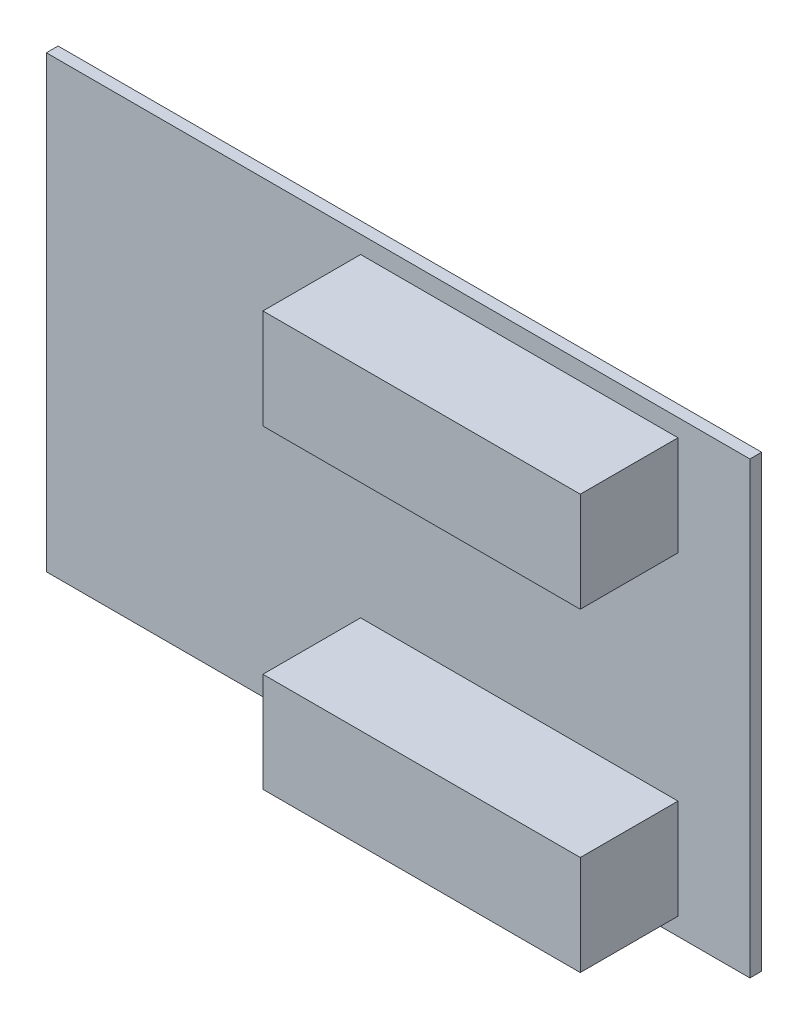
SolidWorks part; units mm, degrees
ref_plane "前视基准面" through (0, 0, 0) normal (0, 0, 1) x (1, 0, 0)
ref_plane "上视基准面" through (0, 0, 0) normal (0, 1, 0) x (1, 0, 0)
ref_plane "右视基准面" through (0, 0, 0) normal (1, 0, 0) x (0, 0, -1)
sketch "草图1" plane through (0, 0, 0) normal (0, 0, 1) x (1, 0, 0)
  line L1 (-90, 57.5) -> (90, 57.5)
  line L2 (-90, 57.5) -> (-90, -57.5)
  line L3 (-90, -57.5) -> (90, -57.5)
  line L4 (90, 57.5) -> (90, -57.5)
  line L5 (-90, 57.5) -> (90, -57.5) construction
  line L6 (-90, -57.5) -> (90, 57.5) construction
  point P0 (0, 0)
  dimension "D1" = 115
  dimension "D2" = 180
extrude "凸台-拉伸1" add sketch "草图1" along normal blind 3
sketch "草图7" plane through (0, 0, 0) normal (0, 0, -1) x (-1, 0, 0)
  line L0 (-90, 57.5) -> (90, 57.5) construction
  line L1 (-69.1, 50.5) -> (7.1, 50.5)
  line L2 (-69.1, 50.5) -> (-69.1, 30)
  line L3 (-69.1, 30) -> (7.1, 30)
  line L4 (7.1, 50.5) -> (7.1, 30)
  line L6 (-90, -57.5) -> (-90, 57.5) construction
  dimension "D1" = 20.5
  dimension "D2" = 76.2
  dimension "D3" = 7
  dimension "D4" = 20.9
extrude "电池位切除-拉伸3" cut sketch "草图7" against normal up to next
sketch "草图8" plane through (0, 0, 3) normal (0, 0, 1) x (1, 0, 0)
  line L12 (69.1, 50.5) -> (69.1, 30) construction
  line L13 (-9.6, 53) -> (71.6, 53)
  line L14 (-9.6, 53) -> (-9.6, 27.5)
  line L15 (-9.6, 27.5) -> (71.6, 27.5)
  line L16 (71.6, 53) -> (71.6, 27.5)
  line L17 (-7.1, 30) -> (-7.1, 50.5) construction
  line L18 (-7.1, 50.5) -> (69.1, 50.5) construction
  line L19 (69.1, 30) -> (-7.1, 30) construction
  line L20 (-7.1, 50.5) -> (69.1, 50.5)
  line L21 (69.1, 30) -> (-7.1, 30)
  line L22 (69.1, 50.5) -> (69.1, 30)
  line L23 (-7.1, 30) -> (-7.1, 50.5) construction
  line L24 (-7.1, 30) -> (-7.1, 50.5)
  dimension "D1" = 2.5
  dimension "D2" = 2.5
  dimension "D3" = 2.5
  dimension "D4" = 2.5
extrude "凸台-拉伸2" add sketch "草图8" along normal blind 25
sketch "草图9" plane through (0, 0, 28) normal (0, 0, 1) x (1, 0, 0)
  line L0 (71.6, 53) -> (-9.6, 53) construction
  line L5 (71.6, 53) -> (-9.6, 53)
  line L6 (-9.6, 27.5) -> (71.6, 27.5) construction
  line L7 (-9.6, 27.5) -> (71.6, 27.5)
  line L8 (71.6, 27.5) -> (71.6, 53) construction
  line L9 (71.6, 27.5) -> (71.6, 53)
  line L10 (-9.6, 53) -> (-9.6, 27.5) construction
  line L11 (-9.6, 53) -> (-9.6, 27.5)
extrude "凸台-拉伸3" add sketch "草图9" against normal blind 2.5
sketch "草图4" plane through (0, 0, 0) normal (0, 0, -1) x (-1, 0, 0)
  line L0 (7.1, 30) -> (7.1, 50.5) construction
  line L5 (7.1, 40.25) -> (84.6307, 40.25) construction
  line L10 (83.2374, -53.4277) -> (79.3374, -53.4277) construction
  line L11 (83.2374, -49.6277) -> (83.2374, -53.4277) construction
  line L12 (79.3374, -49.6277) -> (83.2374, -49.6277) construction
  line L29 (7.1, 36.25) -> (11.1, 36.25)
  line L30 (11.1, 36.25) -> (11.1, 44.25)
  line L31 (11.1, 44.25) -> (7.1, 44.25)
  line L32 (7.1, 44.25) -> (7.1, 36.25)
  dimension "D1" = 8
  dimension "D2" = 4
extrude "切除-拉伸2" cut sketch "草图4" along normal blind 1.6 from surface starting at face at (0, 0, 3)
mirror "镜向1" about plane through (0, 0, 0) normal (0, 1, 0) of "切除-拉伸2", "凸台-拉伸3", "凸台-拉伸2", "电池位切除-拉伸3"
